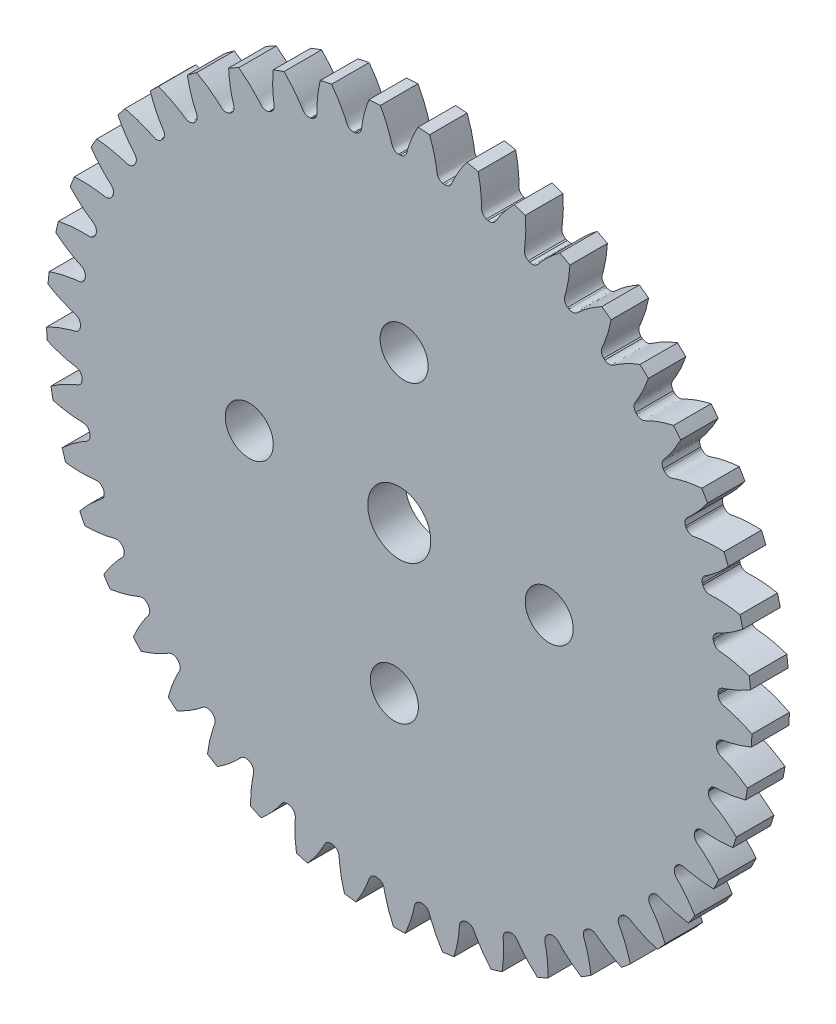
SolidWorks part; units mm, degrees
ref_plane "前视基准面" through (0, 0, 0) normal (0, 0, 1) x (1, 0, 0)
ref_plane "上视基准面" through (0, 0, 0) normal (0, 1, 0) x (1, 0, 0)
ref_plane "右视基准面" through (0, 0, 0) normal (1, 0, 0) x (0, 0, -1)
other "Configuration Table"
sketch "草图1" plane through (0, 0, 0) normal (0, 0, 1) x (1, 0, 0)
  circle A0 centre (0, 0) radius 23.5
extrude "凸台-拉伸1" add sketch "草图1" along normal blind 2.5
ref_axis "基准轴1" through (0, 0, 2.5) along (0, 0, -1)
sketch "草图2" plane through (0, 0, 0) normal (0, 0, 1) x (1, 0, 0)
  line L0 (0, 0) -> (0, 23.5) construction
  circle A0 centre (0, 0) radius 23.5 construction
  arc A1 (0.0519, 21.2499) -> (-0.0519, 21.2499) centre (0, 0) ccw
  arc A2 (3.8286, 26.7057) -> (-3.8286, 26.7057) centre (0, 0) ccw
  spline S0 degree 3 poles (0.0519, 21.2499) (0.4436, 21.3041) (0.4881, 21.5947) (0.5806, 21.9096) (0.6162, 22.0237) (0.6568, 22.145) (0.7027, 22.2735) (0.7541, 22.4089) (0.8114, 22.5512) (0.8748, 22.7) (0.9447, 22.8553) (1.0213, 23.0167) (1.1048, 23.1842) (1.1956, 23.3575) (1.294, 23.5363) (1.4001, 23.7204) (1.5142, 23.9097) (1.6367, 24.1037) (1.7676, 24.3024) (1.9073, 24.5053) (2.0559, 24.7123) (2.2137, 24.923) (2.3809, 25.1372) (2.5577, 25.3546) (2.7442, 25.5749) (2.9408, 25.7977) (3.1474, 26.0228) (3.4406, 26.3296) (3.6704, 26.5559) (3.8286, 26.7057) knots 0 0 0 0 0.112268 0.128789 0.146568 0.165606 0.185901 0.207456 0.230268 0.254339 0.279668 0.306255 0.334101 0.363205 0.393567 0.425188 0.458067 0.492204 0.527599 0.564253 0.602166 0.641336 0.681765 0.723452 0.766398 0.810601 0.856064 0.902784 1 1 1 1
  spline S1 degree 3 poles (-0.0519, 21.2499) (-0.4436, 21.3041) (-0.4881, 21.5947) (-0.5806, 21.9096) (-0.6162, 22.0237) (-0.6568, 22.145) (-0.7027, 22.2735) (-0.7541, 22.4089) (-0.8114, 22.5512) (-0.8748, 22.7) (-0.9447, 22.8553) (-1.0213, 23.0167) (-1.1048, 23.1842) (-1.1956, 23.3575) (-1.294, 23.5363) (-1.4001, 23.7204) (-1.5142, 23.9097) (-1.6367, 24.1037) (-1.7676, 24.3024) (-1.9073, 24.5053) (-2.0559, 24.7123) (-2.2137, 24.923) (-2.3809, 25.1372) (-2.5577, 25.3546) (-2.7442, 25.5749) (-2.9408, 25.7977) (-3.1474, 26.0228) (-3.4406, 26.3296) (-3.6704, 26.5559) (-3.8286, 26.7057) knots 0 0 0 0 0.112268 0.128789 0.146568 0.165606 0.185901 0.207456 0.230268 0.254339 0.279668 0.306255 0.334101 0.363205 0.393567 0.425188 0.458067 0.492204 0.527599 0.564253 0.602166 0.641336 0.681765 0.723452 0.766398 0.810601 0.856064 0.902784 1 1 1 1
extrude "切除-拉伸1" cut sketch "草图2" along normal through all
pattern_circular "阵列(圆周)1" count 45 over 360 about axis through (0, 0, 2.5) along (0, 0, -1) of "切除-拉伸1"
sketch "草图3" plane through (0, 0, 0) normal (0, 0, 1) x (1, 0, 0)
  circle A0 centre (0, 0) radius 22.5 construction
  dimension "Dn" = 45
sketch "草图4" plane through (0, 0, 2.5) normal (0, 0, 1) x (1, 0, 0)
  circle A0 centre (0, 0) radius 2.1
  dimension "D1" = 4.2
extrude "切除-拉伸2" cut sketch "草图4" against normal blind 10
sketch "草图5" plane through (0, 0, 2.5) normal (0, 0, 1) x (1, 0, 0)
  line L0 (-21.2388, 0.6898) -> (0, 0) construction
  circle A0 centre (0, 0) radius 10 construction
  circle A5 centre (-9.9947, 0.3246) radius 1.6
  circle A7 centre (0, 0) radius 10 construction
  circle A8 centre (0.3246, 9.9947) radius 1.6
  circle A9 centre (0, 0) radius 10 construction
  circle A10 centre (9.9947, -0.3246) radius 1.6
  circle A11 centre (0, 0) radius 10 construction
  circle A12 centre (-0.3246, -9.9947) radius 1.6
  point P6 (-21.2388, 0.6898)
  point P21 (0, 0)
  dimension "D1" = 20
  dimension "D2" = 3.2
  dimension "D3" = 4
extrude "切除-拉伸3" cut sketch "草图5" against normal blind 10
sketch "草图6" plane through (0, 0, 2.5) normal (0, 0, 1) x (1, 0, 0)
  line L0 (-21.2388, 0.6898) -> (-9.9947, 0.3246)
  line L1 (-9.9947, 0.3246) -> (24.4846, -0.7952)
